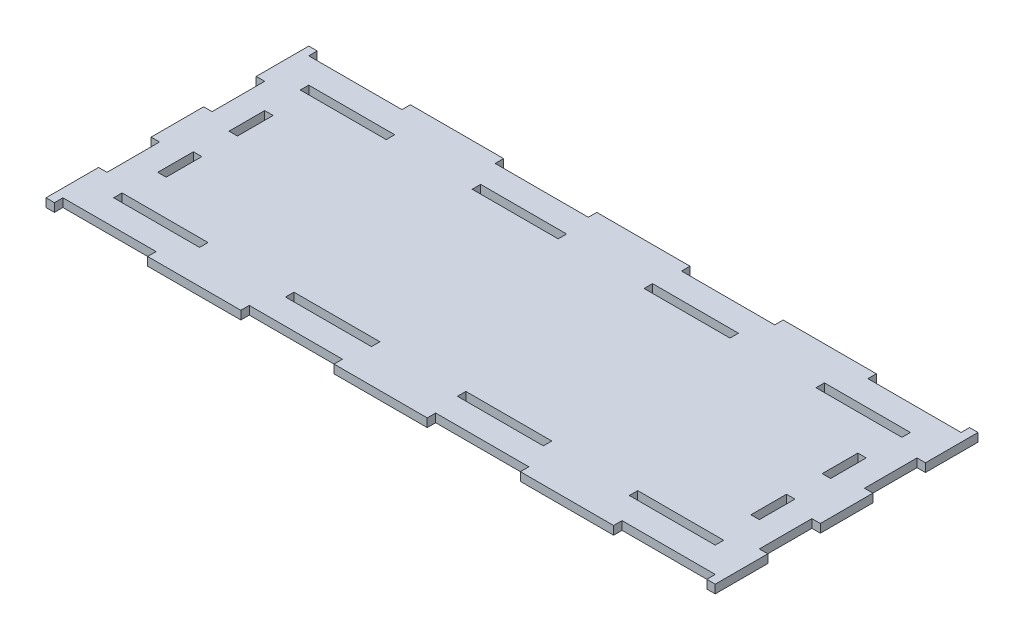
SolidWorks part; units mm, degrees
ref_plane "Front Plane" through (0, 0, 0) normal (0, 0, 1) x (1, 0, 0)
ref_plane "Top Plane" through (0, 0, 0) normal (0, 1, 0) x (1, 0, 0)
ref_plane "Right Plane" through (0, 0, 0) normal (1, 0, 0) x (0, 0, -1)
sketch "Sketch1" plane through (0, 0, 0) normal (0, 1, 0) x (1, 0, 0)
  line L1 (-207.5, -63.25) -> (207.5, -63.25)
  line L2 (-207.5, -63.25) -> (-207.5, 63.25)
  line L3 (-207.5, 63.25) -> (207.5, 63.25)
  line L4 (207.5, -63.25) -> (207.5, 63.25)
  line L5 (-207.5, -63.25) -> (207.5, 63.25) construction
  line L6 (-207.5, 63.25) -> (207.5, -63.25) construction
  point P0 (0, 0)
  point P6 (-169.9468, 63.25)
  dimension "D1" = 126.5
  dimension "D2" = 415
extrude "Boss-Extrude1" add sketch "Sketch1" along normal blind 6
sketch "Sketch2" plane through (0, 6, 0) normal (0, 1, 0) x (1, 0, 0)
  line L0 (213.5, -69.25) -> (213.5, 69.25)
  line L3 (-213.5, -69.25) -> (213.5, -69.25)
  line L4 (207.5, -63.25) -> (207.5, 63.25)
  line L5 (207.5, 63.25) -> (-207.5, 63.25)
  line L6 (-207.5, 63.25) -> (-207.5, -63.25)
  line L7 (-207.5, -63.25) -> (207.5, -63.25)
  line L8 (207.5, -63.25) -> (207.5, 63.25)
  line L9 (207.5, 63.25) -> (-207.5, 63.25)
  line L10 (-207.5, 63.25) -> (-207.5, -63.25)
  line L11 (-207.5, -63.25) -> (207.5, -63.25)
  line L12 (231.5, -87.25) -> (231.5, 87.25)
  line L13 (231.5, 87.25) -> (-231.5, 87.25)
  line L14 (-231.5, 87.25) -> (-231.5, -87.25)
  line L15 (-231.5, -87.25) -> (231.5, -87.25)
  line L16 (237.5, -93.25) -> (237.5, 93.25)
  line L19 (-237.5, -93.25) -> (237.5, -93.25)
  line L20 (213.5, 69.25) -> (-213.5, 69.25) construction
  line L21 (-213.5, 69.25) -> (-213.5, -69.25) construction
  line L22 (-213.5, -69.25) -> (-213.5, -63.25)
  line L27 (152.5, 69.25) -> (91.5, 69.25)
  line L28 (152.5, 69.25) -> (152.5, 63.25)
  line L29 (152.5, 63.25) -> (91.5, 63.25)
  line L30 (91.5, 69.25) -> (91.5, 63.25)
  line L31 (91.5, 69.25) -> (30.5, 69.25)
  line L32 (91.5, 69.25) -> (91.5, 63.25)
  line L33 (91.5, 63.25) -> (30.5, 63.25)
  line L34 (30.5, 69.25) -> (30.5, 63.25)
  line L35 (30.5, 69.25) -> (-30.5, 69.25)
  line L36 (30.5, 69.25) -> (30.5, 63.25)
  line L37 (30.5, 63.25) -> (-30.5, 63.25)
  line L38 (-30.5, 69.25) -> (-30.5, 63.25)
  line L39 (-30.5, 69.25) -> (-91.5, 69.25)
  line L40 (-30.5, 69.25) -> (-30.5, 63.25)
  line L41 (-30.5, 63.25) -> (-91.5, 63.25)
  line L42 (-91.5, 69.25) -> (-91.5, 63.25)
  line L43 (-91.5, 69.25) -> (-152.5, 69.25)
  line L44 (-91.5, 69.25) -> (-91.5, 63.25)
  line L45 (-91.5, 63.25) -> (-152.5, 63.25)
  line L46 (-152.5, 69.25) -> (-152.5, 63.25)
  line L47 (-152.5, 69.25) -> (-213.5, 69.25)
  line L48 (-152.5, 69.25) -> (-152.5, 63.25)
  line L49 (-152.5, 63.25) -> (-213.5, 63.25)
  line L50 (-213.5, 69.25) -> (-213.5, 63.25)
  line L51 (-213.5, 63.25) -> (-207.5, 63.25)
  line L52 (-213.5, 63.25) -> (-213.5, 37.95)
  line L53 (-213.5, 37.95) -> (-207.5, 37.95)
  line L54 (-207.5, 63.25) -> (-207.5, 37.95)
  line L55 (-207.5, 37.95) -> (-213.5, 37.95)
  line L56 (-207.5, 37.95) -> (-207.5, 12.65)
  line L57 (-207.5, 12.65) -> (-213.5, 12.65)
  line L58 (-213.5, 37.95) -> (-213.5, 12.65)
  line L59 (-213.5, 12.65) -> (-207.5, 12.65)
  line L60 (-213.5, 12.65) -> (-213.5, -12.65)
  line L61 (-213.5, -12.65) -> (-207.5, -12.65)
  line L62 (-207.5, 12.65) -> (-207.5, -12.65)
  line L63 (-207.5, -12.65) -> (-213.5, -12.65)
  line L64 (-207.5, -12.65) -> (-207.5, -37.95)
  line L65 (-207.5, -37.95) -> (-213.5, -37.95)
  line L66 (-213.5, -12.65) -> (-213.5, -37.95)
  line L67 (-213.5, -37.95) -> (-207.5, -37.95)
  line L68 (-213.5, -37.95) -> (-213.5, -63.25)
  line L69 (-213.5, -63.25) -> (-207.5, -63.25)
  line L70 (-207.5, -37.95) -> (-207.5, -63.25)
  line L71 (152.5, 63.25) -> (213.5, 63.25)
  line L72 (152.5, 63.25) -> (152.5, 69.25)
  line L73 (152.5, 69.25) -> (213.5, 69.25)
  line L74 (213.5, 63.25) -> (213.5, 69.25)
  line L75 (-237.5, 93.25) -> (-231.5, 93.25)
  line L76 (-237.5, 93.25) -> (-237.5, 55.95)
  line L77 (-237.5, 55.95) -> (-231.5, 55.95)
  line L78 (-231.5, 93.25) -> (-231.5, 55.95)
  line L79 (-237.5, 93.25) -> (-237.5, -93.25) construction
  line L80 (-231.5, 55.95) -> (-237.5, 55.95)
  line L81 (-231.5, 55.95) -> (-231.5, 18.65)
  line L82 (-231.5, 18.65) -> (-237.5, 18.65)
  line L83 (-237.5, 55.95) -> (-237.5, 18.65)
  line L84 (-237.5, 18.65) -> (-231.5, 18.65)
  line L85 (-237.5, 18.65) -> (-237.5, -18.65)
  line L86 (-237.5, -18.65) -> (-231.5, -18.65)
  line L87 (-231.5, 18.65) -> (-231.5, -18.65)
  line L88 (-231.5, -18.65) -> (-237.5, -18.65)
  line L89 (-231.5, -18.65) -> (-231.5, -55.95)
  line L90 (-231.5, -55.95) -> (-237.5, -55.95)
  line L91 (-237.5, -18.65) -> (-237.5, -55.95)
  line L92 (-237.5, -55.95) -> (-231.5, -55.95)
  line L93 (-237.5, -55.95) -> (-237.5, -93.25)
  line L94 (-237.5, -93.25) -> (-231.5, -93.25)
  line L95 (-231.5, -55.95) -> (-231.5, -93.25)
  line L96 (231.5, 87.25) -> (165.3571, 87.25)
  line L97 (231.5, 87.25) -> (231.5, 93.25)
  line L98 (231.5, 93.25) -> (165.3571, 93.25)
  line L99 (165.3571, 87.25) -> (165.3571, 93.25)
  line L100 (165.3571, 93.25) -> (99.2143, 93.25)
  line L101 (165.3571, 93.25) -> (165.3571, 87.25)
  line L102 (165.3571, 87.25) -> (99.2143, 87.25)
  line L103 (99.2143, 93.25) -> (99.2143, 87.25)
  line L104 (99.2143, 87.25) -> (33.0714, 87.25)
  line L105 (99.2143, 87.25) -> (99.2143, 93.25)
  line L106 (99.2143, 93.25) -> (33.0714, 93.25)
  line L107 (33.0714, 87.25) -> (33.0714, 93.25)
  line L108 (33.0714, 93.25) -> (-33.0714, 93.25)
  line L109 (33.0714, 93.25) -> (33.0714, 87.25)
  line L110 (33.0714, 87.25) -> (-33.0714, 87.25)
  line L111 (-33.0714, 93.25) -> (-33.0714, 87.25)
  line L112 (-33.0714, 87.25) -> (-99.2143, 87.25)
  line L113 (-33.0714, 87.25) -> (-33.0714, 93.25)
  line L114 (-33.0714, 93.25) -> (-99.2143, 93.25)
  line L115 (-99.2143, 87.25) -> (-99.2143, 93.25)
  line L116 (-99.2143, 93.25) -> (-165.3571, 93.25)
  line L117 (-99.2143, 93.25) -> (-99.2143, 87.25)
  line L118 (-99.2143, 87.25) -> (-165.3571, 87.25)
  line L119 (-165.3571, 93.25) -> (-165.3571, 87.25)
  line L120 (-165.3571, 87.25) -> (-231.5, 87.25)
  line L121 (-165.3571, 87.25) -> (-165.3571, 93.25)
  line L122 (-165.3571, 93.25) -> (-231.5, 93.25)
  line L123 (-231.5, 87.25) -> (-231.5, 93.25)
  line L124 (237.5, 93.25) -> (-237.5, 93.25) construction
  line L125 (237.5, 93.25) -> (231.5, 93.25)
  line M94 (-207.5, 63.25) -> (-207.5, -63.25)
  dimension "D1" = 0
  dimension "D2" = 6
  dimension "D3" = 18
  dimension "D4" = 6
extrude "Boss-Extrude2" add sketch "Sketch2" against normal blind 6 contours L27 L30 L9 L28 | L43 L46 L9 L42 | L35 L38 L9 L34 | L14 L15 L12 L13 L27 L73 L0 L3 L22 L68 L66 L60 L58 L52 L50 L47 L43 L39 L35 L31 | L116 L119 L13 L115 | L108 L111 L13 L107 | L100 L103 L13 L99 | L52 L53 L49 M94 | L78 L75 L76 L77 L14 | L60 L61 L57 M94 | L85 L86 L14 L82 | L68 L69 L65 M94 | L95 L14 L90 L93 L19 region at (-210.5, 6, 50.6) region at (122, 6, -66.25) region at (-210.5, 6, 0) region at (0, 6, -66.25) region at (-210.5, 6, -50.6) region at (-122, 6, -66.25) region at (0, 6, 82.3021) region at (-234.5, 6, 74.6) region at (132.2857, 6, -90.25) region at (-234.5, 6, 0) region at (0, 6, -90.25) region at (-234.5, 6, -74.6) region at (-132.2857, 6, -90.25)
mirror "Mirror2" about plane through (0, 0, 0) normal (0, 0, 1) of "Boss-Extrude2"
mirror "Mirror3" about plane through (0, 0, 0) normal (1, 0, 0) of "Boss-Extrude2"
